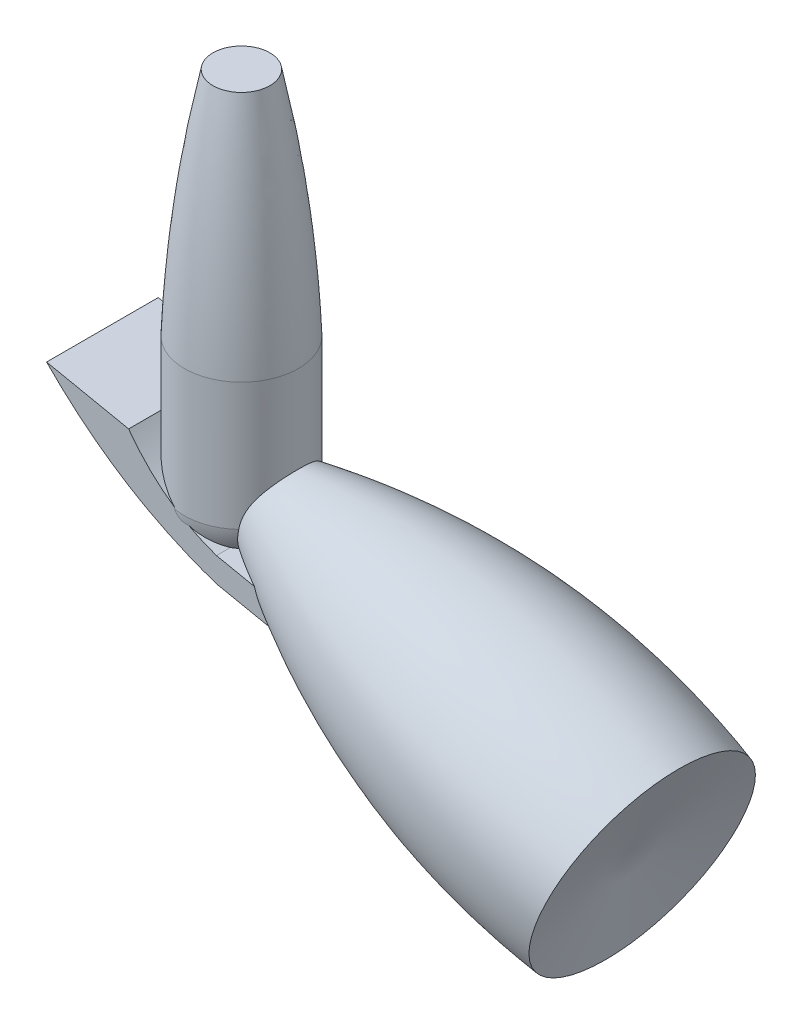
SolidWorks part; units mm, degrees
ref_plane "Alzado" through (0, 0, 0) normal (0, 0, 1) x (1, 0, 0)
ref_plane "Planta" through (0, 0, 0) normal (0, 1, 0) x (1, 0, 0)
ref_plane "Vista lateral" through (0, 0, 0) normal (1, 0, 0) x (0, 0, -1)
sketch "Croquis1" plane through (0, 0, 0) normal (0, 0, 1) x (1, 0, 0)
  line L0 (-7.0332, -46.6722) -> (-7.0332, -55.0755)
  line L1 (-10.0928, -11.6722) -> (-7.0332, -11.6722)
  line L2 (-13.1523, -36.4779) -> (-13.1523, -50.179)
  line L3 (-7.0332, -55.0755) -> (-10.0928, -55.0755)
  line L4 (-7.0332, -11.6722) -> (-7.0332, -46.6722)
  spline S0 degree 2 poles (-10.0928, -55.0755) (-12.8396, -53.4154) (-13.1523, -50.179) knots 0 0 0 1 1 1
  spline S2 degree 2 poles (-10.0928, -11.6722) (-12.6793, -23.9441) (-13.1523, -36.4779) knots 0 0 0 1 1 1
  dimension "D1" = 35
revolve "Revolución1" add sketch "Croquis1" angle 360 about L4
sketch "Croquis4" plane through (0, 0, 0) normal (0, 0, 1) x (1, 0, 0)
  line L0 (-2.5438, -50.179) -> (34.7432, -63.6732)
  line L1 (-13.1523, -50.179) -> (-0.9141, -50.179) construction
  line L2 (-4.9744, -53.6296) -> (-3.9737, -49.6615)
  line L3 (34.7432, -63.6732) -> (32.113, -74.9757)
  line L4 (-2.5438, -50.179) -> (-3.9737, -49.6615)
  spline S2 degree 2 poles (-4.9744, -53.6296) (10.4847, -69.6619) (32.113, -74.9757) knots 0 0 0 1 1 1
revolve "Revolución3" add sketch "Croquis4" angle 360 about L0
sketch "Croquis5" plane through (0, 0, 0) normal (0, 0, 1) x (1, 0, 0)
  line L0 (-13.1523, -50.179) -> (-2.8524, -50.179) construction
  line L1 (-21.9731, -43.3931) -> (-13.1523, -45.2076)
  line L2 (-13.1523, -36.4779) -> (-13.1523, -50.179) construction
  line L4 (-3.7124, -54.9103) -> (4.3262, -56.5639)
  line L5 (4.3262, -56.5639) -> (4.8453, -54.0409)
  line L7 (-3.7124, -52.2805) -> (4.8453, -54.0409)
  spline S0 degree 3 poles (-3.7124, -54.9103) (-3.7119, -54.9108) (-3.6607, -54.9616) (-3.5587, -55.0626) (-3.406, -55.2131) (-3.253, -55.363) (-3.0997, -55.5124) (-2.9462, -55.6613) (-2.7923, -55.8098) (-2.6381, -55.9577) (-2.4846, -56.1042) (-2.3317, -56.2494) (-2.1795, -56.3932) (-2.027, -56.5365) (-1.8732, -56.6802) (-1.7183, -56.8243) (-1.5621, -56.9687) (-1.4057, -57.1126) (-1.249, -57.256) (-1.0929, -57.3981) (-0.9374, -57.5388) (-0.7826, -57.6782) (-0.6276, -57.8171) (-0.4624, -57.9643) (-0.287, -58.1197) (-0.1013, -58.2832) (0.0848, -58.4459) (0.2713, -58.608) (0.4582, -58.7694) (0.6365, -58.9224) (0.806, -59.067) (0.9668, -59.2034) (1.1279, -59.3393) (1.2892, -59.4747) (1.4499, -59.6088) (1.6099, -59.7416) (1.7692, -59.8731) (1.9288, -60.0041) (2.0989, -60.1429) (2.2794, -60.2894) (2.4705, -60.4435) (2.662, -60.5969) (2.8539, -60.7496) (3.0462, -60.9016) (3.2388, -61.0529) (3.4319, -61.2035) (3.6254, -61.3535) (3.8193, -61.5027) (4.0135, -61.6513) (4.2082, -61.7992) (4.3995, -61.9436) (4.5875, -62.0845) (4.7722, -62.2221) (4.9572, -62.359) (5.1425, -62.4953) (5.3224, -62.6268) (5.4969, -62.7536) (5.666, -62.8756) (5.8353, -62.9972) (6.0049, -63.1182) (6.1738, -63.2381) (6.3419, -63.3567) (6.5094, -63.4741) (6.6771, -63.5911) (6.8557, -63.7149) (7.0454, -63.8456) (7.2461, -63.9829) (7.4473, -64.1195) (7.6488, -64.2554) (7.8507, -64.3907) (8.0531, -64.5252) (8.2558, -64.6591) (8.4589, -64.7923) (8.6624, -64.9248) (8.8664, -65.0566) (9.0707, -65.1877) (9.2715, -65.3157) (9.4688, -65.4405) (9.6625, -65.5622) (9.8566, -65.6833) (10.051, -65.8038) (10.2497, -65.9262) (10.4527, -66.0503) (10.6601, -66.1761) (10.8679, -66.3012) (11.076, -66.4256) (11.2846, -66.5494) (11.4896, -66.6701) (11.6909, -66.7878) (11.8886, -66.9026) (12.0867, -67.0167) (12.2852, -67.1303) (12.4839, -67.2432) (12.6831, -67.3556) (12.8826, -67.4673) (13.0824, -67.5784) (13.2826, -67.6889) (13.4819, -67.7981) (13.6804, -67.9061) (13.8781, -68.0129) (14.0761, -68.119) (14.2693, -68.2219) (14.4579, -68.3215) (14.6416, -68.418) (14.8257, -68.5139) (15.01, -68.6094) (15.1936, -68.7038) (15.3763, -68.7971) (15.5582, -68.8894) (15.7404, -68.9812) (15.9344, -69.0783) (16.1404, -69.1806) (16.3584, -69.288) (16.5767, -69.3947) (16.7955, -69.5007) (17.0147, -69.606) (17.2342, -69.7106) (17.4542, -69.8146) (17.6745, -69.9178) (17.8953, -70.0204) (18.1164, -70.1223) (18.338, -70.2234) (18.5557, -70.322) (18.7695, -70.4181) (18.9795, -70.5116) (19.1898, -70.6045) (19.4005, -70.6968) (19.6158, -70.7903) (19.8357, -70.885) (20.0603, -70.9809) (20.2853, -71.0761) (20.5107, -71.1706) (20.7364, -71.2644) (20.9583, -71.3557) (21.1762, -71.4447) (21.3902, -71.5312) (21.6045, -71.6172) (21.8192, -71.7025) (22.0342, -71.7872) (22.2496, -71.8714) (22.4653, -71.9549) (22.6814, -72.0377) (22.8979, -72.12) (23.1134, -72.2012) (23.3279, -72.2813) (23.5415, -72.3603) (23.7555, -72.4387) (23.9754, -72.5187) (24.2015, -72.6) (24.4337, -72.6827) (24.6663, -72.7647) (24.8992, -72.8461) (25.1326, -72.9267) (25.3619, -73.0051) (25.5871, -73.0814) (25.8082, -73.1555) (26.0297, -73.2291) (26.2515, -73.302) (26.4737, -73.3743) (26.6962, -73.446) (26.9191, -73.5171) (27.1423, -73.5875) (27.3659, -73.6574) (27.5885, -73.7262) (27.8101, -73.794) (28.0307, -73.8609) (28.2517, -73.9271) (28.4743, -73.9932) (28.6987, -74.059) (28.9247, -74.1246) (29.1511, -74.1896) (29.3778, -74.254) (29.6035, -74.3174) (29.8282, -74.3798) (30.0519, -74.4413) (30.276, -74.5022) (30.5019, -74.5629) (30.7297, -74.6233) (30.9594, -74.6836) (31.1894, -74.7433) (31.4198, -74.8024) (31.6505, -74.8608) (31.8816, -74.9187) (32.0358, -74.9567) (32.113, -74.9757) knots 0 0 0 0 0.000045 0.005204 0.010359 0.01551 0.020658 0.025803 0.030944 0.036082 0.041216 0.046256 0.051292 0.056325 0.061356 0.066474 0.071589 0.076702 0.081811 0.086917 0.091929 0.096939 0.101945 0.106949 0.112902 0.118852 0.124797 0.130739 0.136678 0.142612 0.147685 0.152756 0.157824 0.16289 0.167953 0.172923 0.177891 0.182857 0.187821 0.193727 0.19963 0.205531 0.211428 0.217323 0.223215 0.229104 0.234991 0.240875 0.246756 0.252635 0.258512 0.264051 0.269587 0.275122 0.280655 0.286186 0.291201 0.296215 0.301228 0.306239 0.311249 0.316168 0.321086 0.326003 0.330919 0.336769 0.342619 0.348466 0.354312 0.360157 0.366001 0.371843 0.377684 0.383525 0.389364 0.395202 0.401039 0.406542 0.412044 0.417546 0.423047 0.428548 0.434381 0.440214 0.446047 0.451879 0.457711 0.463542 0.469041 0.474539 0.480037 0.485535 0.491034 0.496532 0.50203 0.507529 0.513028 0.518528 0.523929 0.529331 0.534734 0.540137 0.545127 0.550118 0.55511 0.560103 0.565096 0.57 0.574905 0.579811 0.584718 0.59056 0.596404 0.602249 0.608095 0.613942 0.619791 0.625642 0.631494 0.637347 0.643203 0.64906 0.654919 0.660445 0.665972 0.671502 0.677033 0.682566 0.688437 0.694309 0.700185 0.706062 0.711942 0.717824 0.723373 0.728923 0.734477 0.740032 0.74559 0.751151 0.756714 0.76228 0.767848 0.773419 0.778893 0.784371 0.78985 0.795333 0.801257 0.807184 0.813115 0.819049 0.824986 0.830928 0.836533 0.842142 0.847754 0.853369 0.858988 0.86461 0.870236 0.875866 0.881499 0.887136 0.892676 0.898219 0.903767 0.909318 0.914974 0.920634 0.926298 0.931966 0.937638 0.943213 0.948793 0.954376 0.959963 0.965669 0.97138 0.977095 0.982814 0.988538 0.994267 1 1 1 1 construction
  spline S1 degree 2 poles (-21.9731, -43.3931) (-14.1816, -51.3791) (-3.7124, -54.9103) knots 0 0 0 1 1 1
  spline S2 degree 2 poles (-13.1523, -45.2076) (-9.4979, -50.2634) (-3.7124, -52.2805) knots 0 0 0 1 1 1
extrude "Saliente-Extruir2" add sketch "Croquis5" along normal blind 6 and the other way blind 6
sketch "Croquis6" plane through (0, 0, 6) normal (0, 0, 1) x (1, 0, 0)
  line L0 (-13.1834, -50.4708) -> (-12.788, -55.7163)
  line L1 (-12.788, -55.7163) -> (-3.7124, -55.7163)
  line L2 (-3.7124, -55.7163) -> (-3.7124, -54.9103)
  parabola Q0 (-21.9731, -43.3931) -> (-3.7124, -54.9103) focus (-1.1478, -31.5643) apex (-12.6921, -50.7704) construction
  parabola Q1 (-21.9731, -43.3931) -> (-3.7124, -54.9103) focus (-1.1478, -31.5643) apex (-12.6921, -50.7704) construction
  spline S0 degree 2 poles (-3.7124, -54.9103) (-8.7057, -53.2337) (-13.1834, -50.4708) knots 0 0 0 1 1 1
extrude "Cortar-Extruir4" cut sketch "Croquis6" against normal blind 12
